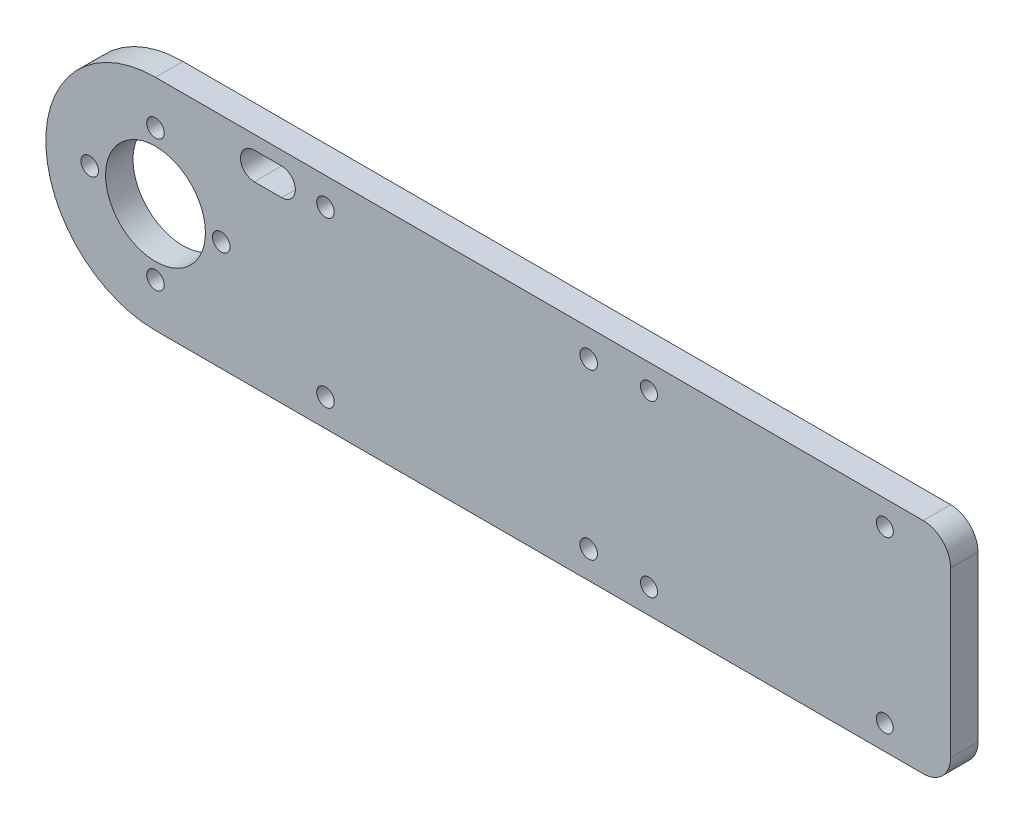
SolidWorks part; units mm, degrees
material "Acrylic (Medium-high impact)"
ref_plane "Front Plane" through (0, 0, 0) normal (0, 0, 1) x (1, 0, 0)
ref_plane "Top Plane" through (0, 0, 0) normal (0, 1, 0) x (1, 0, 0)
ref_plane "Right Plane" through (0, 0, 0) normal (1, 0, 0) x (0, 0, -1)
sketch "Sketch2" plane through (0, 0, 0) normal (0, 0, 1) x (1, 0, 0)
  line L0 (0, 20) -> (0, -20)
  line L1 (0, 20) -> (145, 20)
  line L2 (0, -20) -> (145, -20)
  line L3 (145, 20) -> (145, -20)
  line L4 (0, 0) -> (-20, 0)
  circle A0 centre (0, 0) radius 20
  circle A1 centre (0, 0) radius 9.1
  dimension "D1" = 40
  dimension "D3" = 18.2
  dimension "D2" = 165
extrude "Boss-Extrude1" add sketch "Sketch2" along normal mid plane 5 contours A1 L0 A0 | A0 L2 L3 L1 | A1 L4 A0 L0 | A1 L0 A0 L4 region at (9.696, 0, 0) region at (80.2769, 0, 0) region at (-9.696, 9.696, 0) region at (-9.696, -9.696, 0)
fillet "Fillet1" radius 5 2 edges at (145, -20, 0) (145, 20, 0)
sketch "Sketch3" plane through (0, 0, -2.5) normal (0, 0, -1) x (-1, 0, 0)
  line L0 (-111.5, 20) -> (-111.5, -20)
  line L1 (-111.5, 0) -> (-90, 0)
  line L2 (-90, 0) -> (-90, 15.5)
  line L3 (-145, 15) -> (-145, -15)
  line L4 (-140, -20) -> (0, -20)
  line L5 (0, 20) -> (-140, 20)
  line L6 (-145, 15) -> (-145, -15)
  line L7 (-140, -20) -> (0, -20)
  line L8 (0, 20) -> (-140, 20)
  line L9 (-111.5, 0) -> (-55, 0)
  line L10 (-55, 0) -> (-55, 15)
  line L11 (-55, 15) -> (-79, 15)
  line L12 (0, 0) -> (0, 12)
  line L13 (-31, 15) -> (-23, 15)
  line L14 (-23, 15) -> (-18, 15) construction
  line L17 (-23, 17.5) -> (-18, 17.5)
  line L18 (-23, 12.5) -> (-18, 12.5)
  circle A0 centre (0, 0) radius 12
  circle A1 centre (-90, 15.5) radius 1.55
  circle A2 centre (-90, -15.5) radius 1.55
  arc A3 (-145, -15) -> (-140, -20) centre (-140, -15) ccw
  arc A4 (0, -20) -> (0, 20) centre (0, 0) ccw
  arc A5 (-140, 20) -> (-145, 15) centre (-140, 15) ccw
  arc A6 (-145, -15) -> (-140, -20) centre (-140, -15) ccw
  arc A7 (0, -20) -> (0, 20) centre (0, 0) ccw
  arc A8 (-140, 20) -> (-145, 15) centre (-140, 15) ccw
  circle A9 centre (-133, -15.5) radius 1.55
  circle A10 centre (-133, 15.5) radius 1.55
  circle A11 centre (-79, 15) radius 1.6
  circle A12 centre (-79, -15) radius 1.6
  circle A13 centre (-31, -15) radius 1.6
  circle A14 centre (-31, 15) radius 1.6
  circle A15 centre (0, 12) radius 1.6
  circle A16 centre (12, 0) radius 1.6
  circle A17 centre (0, -12) radius 1.6
  circle A18 centre (-12, 0) radius 1.6
  arc A21 (-23, 17.5) -> (-23, 12.5) centre (-23, 15) ccw
  arc A22 (-18, 12.5) -> (-18, 17.5) centre (-18, 15) ccw
  point P35 (-20.5, 15)
  dimension "D2" = 24
  dimension "D6" = 3.1
  dimension "D10" = 3.2
  dimension "D11" = 3.2
  dimension "D13" = 55
  dimension "D3" = 21.5
  dimension "D4" = 15.5
  dimension "D5" = 90
  dimension "D7" = 8
  dimension "D8" = 15
  dimension "D9" = 24
  dimension "D14" = 5
  dimension "D15" = 5
  dimension "D1" = 0
  dimension "D12" = 4
extrude "Cut-Extrude1" cut sketch "Sketch3" against normal through all contours A14 | A13 | A11 | A12 | A0 A16 | A0 A16 | A0 A17 | A2 | A9 | A10 | A1 | A18 | A15 | A17 region at (80.5547, 15, -2.5) region at (-12.6595, 0, -2.5) region at (-11.3021, 0, -2.5) region at (0, -12.6595, -2.5) region at (32.5547, 15, -2.5) region at (79, -15, -2.5) region at (31, -15, -2.5)
extrude "Cut-Extrude2" cut sketch "Sketch3<4>" against normal blind 10 contours L18 A22 L17 A21 region at (20.5, 15, -2.5)
sketch "Sketch3<4>" plane through (0, 0, -2.5) normal (0, 0, -1) x (-1, 0, 0) same geometry as "Sketch3"
